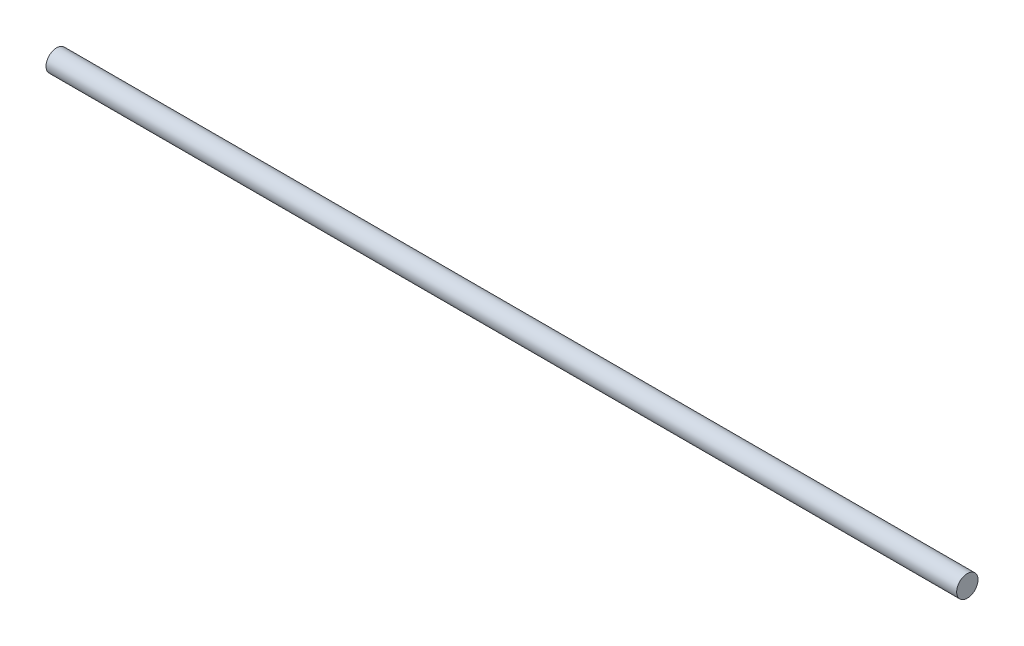
SolidWorks part; units mm, degrees
ref_plane "Front Plane" through (0, 0, 0) normal (0, 0, 1) x (1, 0, 0)
ref_plane "Top Plane" through (0, 0, 0) normal (0, 1, 0) x (1, 0, 0)
ref_plane "Right Plane" through (0, 0, 0) normal (1, 0, 0) x (0, 0, -1)
sketch "Sketch4" plane through (0, 0, 0) normal (1, 0, 0) x (0, 0, -1)
  circle A0 centre (57.6731, 144.1759) radius 3.81
  dimension "D1" = 7.62
extrude "Boss-Extrude2" add sketch "Sketch4" along normal blind 324.612 separate body
